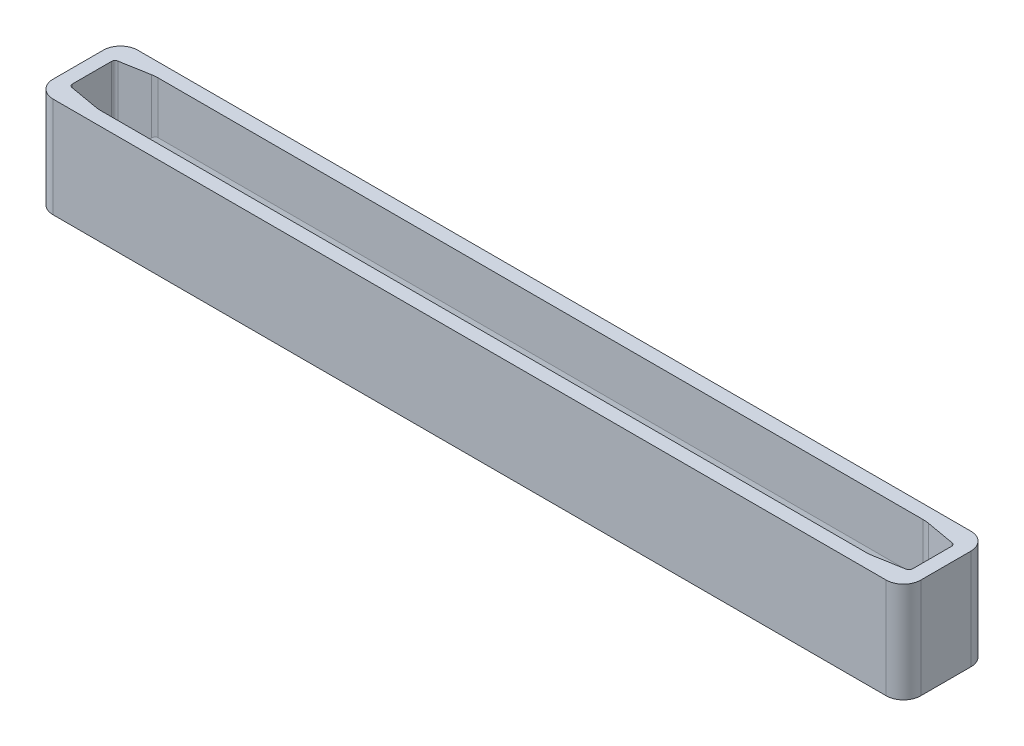
SolidWorks part; units mm, degrees
note: The reader was unsure of these and kept them because the rebuilt part matched: shared geometry of "Sketch1<2>".
ref_plane "Front" through (0, 0, 0) normal (0, 0, 1) x (1, 0, 0)
ref_plane "Top" through (0, 0, 0) normal (0, 1, 0) x (1, 0, 0)
ref_plane "Right" through (0, 0, 0) normal (1, 0, 0) x (0, 0, -1)
sketch "Sketch1" plane through (0, 0, 0) normal (0, 1, 0) x (1, 0, 0)
  line L0 (-125.5, 12.25) -> (125.5, 12.25)
  line L1 (-121.5, -8.25) -> (121.5, -8.25)
  line L2 (-121.5, -8.25) -> (-121.5, 8.25)
  line L3 (-121.5, 8.25) -> (121.5, 8.25)
  line L4 (121.5, -8.25) -> (121.5, 8.25)
  line L5 (-121.5, -8.25) -> (121.5, 8.25) construction
  line L6 (-121.5, 8.25) -> (121.5, -8.25) construction
  line L7 (125.5, -12.25) -> (125.5, 12.25)
  line L8 (-125.5, -12.25) -> (125.5, -12.25)
  line L9 (-125.5, -12.25) -> (-125.5, 12.25)
  point P0 (0, 0)
  dimension "D1" = 243
  dimension "D2" = 16.5
  dimension "D3" = 4
extrude "Boss-Extrude1" add sketch "Sketch1" along normal blind 25
extrude "Boss-Extrude2" add sketch "Sketch1<2>" against normal blind 4 contours L8 L7 L0 L9
sketch "Sketch1<2>" plane through (0, 0, 0) normal (0, 1, 0) x (1, 0, 0) same geometry as "Sketch1"
chamfer "Chamfer1" distance 10 angle 10 6 edges at (-121.5, 12.5, -8.25) (121.5, 12.5, 8.25) (-121.5, 12.5, 8.25) (121.5, 12.5, -8.25) (0, 0, 8.25) (0, 0, -8.25)
fillet "Fillet1" radius 10 4 edges at (111.5, 17.5, 8.25) (111.5, 17.5, -8.25) (-111.5, 17.5, -8.25) (-111.5, 17.5, 8.25)
fillet "Fillet2" radius 1 4 edges at (121.5, 12.5, 6.4867) (121.5, 12.5, -6.4867) (-121.5, 12.5, 6.4867) (-121.5, 12.5, -6.4867)
fillet "Fillet4" radius 10 2 edges at (-121.5, 0, 0) (121.5, 0, 0)
fillet "Fillet5" radius 5 4 edges at (125.5, 10.5, -12.25) (125.5, 10.5, 12.25) (-125.5, 10.5, -12.25) (-125.5, 10.5, 12.25)
